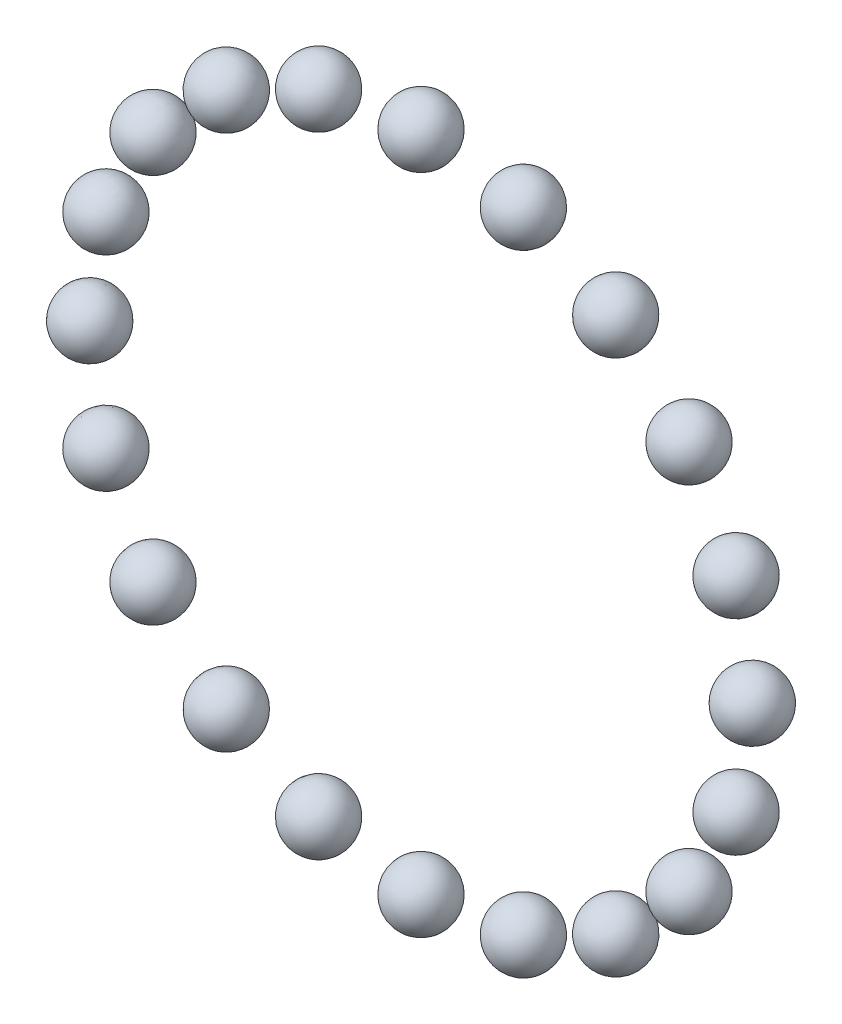
SolidWorks part; units mm, degrees
ref_plane "Front Plane" through (0, 0, 0) normal (0, 0, 1) x (1, 0, 0)
ref_plane "Top Plane" through (0, 0, 0) normal (0, 1, 0) x (1, 0, 0)
ref_plane "Right Plane" through (0, 0, 0) normal (1, 0, 0) x (0, 0, -1)
sketch "Sketch1" plane through (0, 0, 0) normal (0, 0, 1) x (1, 0, 0)
  circle A0 centre (0, 0) radius 32.5
  point P3 (0, 0)
  dimension "D1" = 65
sketch "Sketch2" plane through (0, 0, 0) normal (0, 0, 1) x (1, 0, 0)
  line L0 (-35.5, 0) -> (-29.5, 0)
  circle A0 centre (-32.5, 0) radius 3
  circle A1 centre (0, 0) radius 32.5 construction
  point P6 (0, 0)
  point P7 (0, 0)
  point P8 (0, 0)
  dimension "D1" = 6
ref_axis "Axis1" through (0, 0, 0) along (0, 0, 1)
revolve "Revolve1" add sketch "Sketch2" angle 360 about L0 region at (-32.5, 1.2732, 0)
pattern_circular "CirPattern1" count 20 over 360 about axis through (0, 0, 0) along (0, 0, 1) of bodies 101
